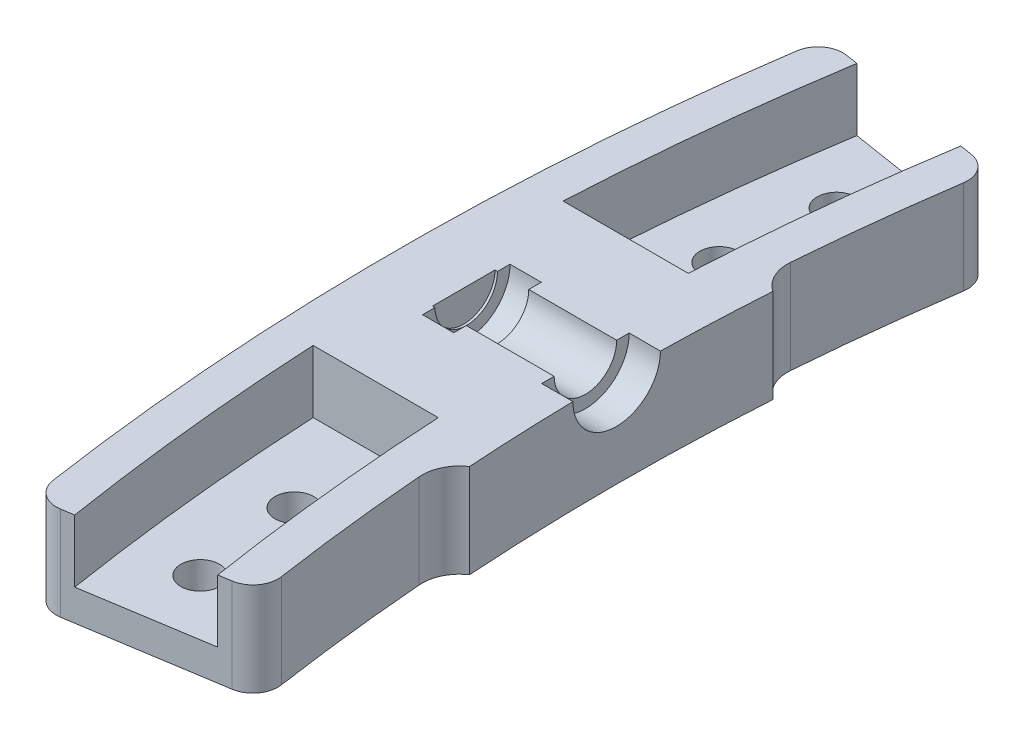
SolidWorks part; units mm, degrees
ref_plane "Front Plane" through (0, 0, 0) normal (0, 0, 1) x (1, 0, 0)
ref_plane "Top Plane" through (0, 0, 0) normal (0, 1, 0) x (1, 0, 0)
ref_plane "Right Plane" through (0, 0, 0) normal (1, 0, 0) x (0, 0, -1)
sketch "Sketch1" plane through (0, 0, 0) normal (0, 1, 0) x (1, 0, 0)
  line L0 (0, 0) -> (-197.5377, -31.2869) construction
  line L1 (0, 0) -> (-197.5377, 31.2869) construction
  line L2 (0, 0) -> (-195, 0) construction
  line L3 (-197.5377, 31.2869) -> (-187.6608, 29.7225)
  line L4 (-187.6608, -29.7225) -> (-197.5377, -31.2869)
  line L5 (0, 0) -> (-200.5007, -31.7562) construction
  line L6 (0, 0) -> (-200.5007, 31.7562) construction
  line L7 (-200.5007, 31.7562) -> (-184.6977, 29.2532)
  line L8 (-200.5007, -31.7562) -> (-184.6977, -29.2532)
  arc A0 (-197.5377, 31.2869) -> (-197.5377, -31.2869) centre (0, 0) ccw
  arc A1 (-187.6608, 29.7225) -> (-187.6608, -29.7225) centre (0, 0) ccw
  arc A2 (-192.5992, -30.5047) -> (-192.5992, 30.5047) centre (0, 0) cw construction
  arc A4 (-184.6977, 29.2532) -> (-184.6977, -29.2532) centre (0, 0) ccw
  arc A5 (-200.5007, 31.7562) -> (-200.5007, -31.7562) centre (0, 0) ccw
  dimension "D1" = 200
  dimension "D2" = 190
  dimension "D3" = 5
  dimension "D5" = 187
  dimension "D6" = 203
  dimension "D4" = 18
extrude "Boss-Extrude1" add sketch "Sketch1" along normal blind 10 contours A1 L3 A0 L4 | L7 A5 L8 A0 | A4 L7 A1 L8 region at (-200.6761, 0, 0) region at (-194.2416, 0, 0) region at (-187.7297, 0, 0)
ref_plane "Plane1" through (-195, 0, 0) normal (1, 0, 0) x (0, 0, -1)
sketch "Sketch15" plane through (0, 10, 0) normal (0, 1, 0) x (1, 0, 0)
  line L0 (-187.6608, -29.7225) -> (-197.5377, -31.2869) construction
  line L1 (-185, 10) -> (-205, 10)
  line L2 (-185, 10) -> (-185, -10)
  line L3 (-185, -10) -> (-205, -10)
  line L4 (-205, 10) -> (-205, -10)
  line L5 (-185, 10) -> (-205, -10) construction
  line L6 (-185, -10) -> (-205, 10) construction
  line L7 (-197.5377, 31.2869) -> (-187.6608, 29.7225) construction
  line L8 (-187.6608, -29.7225) -> (-197.5377, -31.2869)
  line L9 (-197.5377, 31.2869) -> (-187.6608, 29.7225)
  arc A2 (-187.6608, 29.7225) -> (-187.6608, -29.7225) centre (0, 0) ccw construction
  arc A3 (-197.5377, 31.2869) -> (-197.5377, -31.2869) centre (0, 0) ccw construction
  arc A4 (-187.6608, 29.7225) -> (-187.6608, -29.7225) centre (0, 0) ccw
  arc A5 (-197.5377, 31.2869) -> (-197.5377, -31.2869) centre (0, 0) ccw
  point P0 (-195, 0)
  line M5 (-200.5007, -31.7562) -> (-184.6977, -29.2532)
  line M7 (-184.6977, 29.2532) -> (-200.5007, 31.7562)
  dimension "D1" = 20
  dimension "D2" = 20
extrude "Cut-Extrude1" cut sketch "Sketch15" against normal blind 5 contours A5 L1 A4 M7 | L3 A5 A4 M5 region at (-193.9153, 10, -20.2762) region at (-193.9153, 10, 20.2762)
ref_plane "Plane2" through (-195, 0, 0) normal (-1, 0, 0) x (0, 0, 1)
sketch "Sketch12" plane through (0, 0, 0) normal (0, 1, 0) x (1, 0, 0)
  line L0 (0, 0) -> (-194.258, -16.9954) construction
  line L1 (0, 0) -> (-193.3317, -25.4526) construction
  line L2 (0, 0) -> (-195, 0) construction
  line L3 (0, 0) -> (-195, 0) construction
  line L4 (0, 0) -> (-194.258, 16.9954) construction
  line L5 (0, 0) -> (-193.3317, 25.4526) construction
  arc A0 (-192.5992, 30.5047) -> (-192.5992, -30.5047) centre (0, 0) ccw construction
  dimension "D1" = 10
  dimension "D2" = 15
hole_wizard "Ø3.1 (3.1) Diameter Hole2" positions "Sketch18" profile "Sketch17" hole size "Ø3.1" standard "ISO" end condition through all
sketch "Sketch18" plane through (0, 0, 0) normal (0, -1, 0) x (-1, 0, 0)
  point P0 (193.3317, -25.4526)
  point P3 (194.258, -16.9954)
  point P6 (194.258, 16.9954)
  point P9 (193.3317, 25.4526)
sketch "Sketch17" plane through (-193.3317, 0, 25.4526) normal (1, 0, 0) x (0, 0, -1)
  line L0 (0, 0) -> (0, 10)
  line L1 (0, 10) -> (1.55, 10)
  line L2 (1.55, 10) -> (1.55, 0)
  line L5 (1.55, 0) -> (0, 0)
  line L11 (0, -6.35) -> (0, 107.95) construction
  dimension "Thru Hole Dia." = 3.1
  dimension "Thru Hole Depth" = 10
sketch "Sketch19" plane through (0, 0, 0) normal (0, 1, 0) x (1, 0, 0)
  line L0 (0, 0) -> (-185.1028, -12.1323) construction
  line L1 (0, 0) -> (-185.5, 0) construction
  line L2 (-185.1028, -12.1323) -> (-186.5996, -12.2304)
  line L3 (-185.1028, 12.1323) -> (-186.5996, 12.2304)
  arc A0 (-185.1028, 12.1323) -> (-185.1028, -12.1323) centre (0, 0) ccw
  arc A1 (-184.6977, 29.2532) -> (-184.6977, -29.2532) centre (0, 0) ccw construction
  arc A2 (-186.5996, 12.2304) -> (-186.5996, -12.2304) centre (0, 0) ccw
  dimension "D1" = 185.5
  dimension "D2" = 3.75
extrude "Boss-Extrude2" add sketch "Sketch19" along normal blind 10
fillet "Fillet1" radius 3 2 edges at (-186.5996, 5, -12.2304) (-186.5996, 5, 12.2304)
fillet "Fillet2" radius 2 4 edges at (-200.5007, 5, -31.7562) (-200.5007, 5, 31.7562) (-184.6977, 5, 29.2532) (-184.6977, 5, -29.2532)
sketch "Sketch20" plane through (0, 10, 0) normal (0, 1, 0) x (1, 0, 0)
  line L0 (0, 0) -> (-185, 0) construction
  line L1 (-185, 0) -> (-197.5, 0) construction
  dimension "D1" = 185
  dimension "D2" = 12.5
ref_plane "Plane3" through (-197.5, 0, 0) normal (1, 0, 0) x (0, 0, -1)
sketch "Sketch21" plane through (-197.5, 0, 0) normal (1, 0, 0) x (0, 0, -1)
  line L0 (12.1323, 10) -> (-12.1323, 10) construction
  circle A0 centre (0, 10) radius 2.1
  dimension "D1" = 4.2
extrude "Cut-Extrude2" cut sketch "Sketch21" along normal through all
sketch "Sketch22" plane through (-197.5, 0, 0) normal (1, 0, 0) x (0, 0, -1)
  line L0 (-2.1, 10) -> (2.1, 10) construction
  circle A0 centre (0, 10) radius 3.5
  dimension "D1" = 7
extrude "Cut-Extrude3" cut sketch "Sketch22" along normal blind 2.5
sketch "Sketch23" plane through (-197.5, 0, 0) normal (1, 0, 0) x (0, 0, -1)
  line L0 (-3.5, 10) -> (3.5, 10) construction
  circle A0 centre (0, 10) radius 2.5
  dimension "D1" = 5
extrude "Cut-Extrude4" cut sketch "Sketch23" against normal blind 0.2 and the other way blind 2.7
sketch "Sketch24" plane through (0, 10, 0) normal (0, 1, 0) x (1, 0, 0)
  line L0 (-185.5, 0) -> (-197.7, 0) construction
  line L1 (-197.7, -2.5) -> (-197.7, 2.5) construction
  line L3 (-187.967, 0) -> (-185.467, 0)
  line L4 (-187.967, 0) -> (-187.967, 3.5)
  line L5 (-187.967, 3.5) -> (-185.467, 3.5)
  line L6 (-185.467, 0) -> (-185.467, 3.5)
  arc A0 (-185.4881, 2.1) -> (-185.4881, -2.1) centre (0, 0) ccw construction
  arc A1 (-185.1028, 12.1323) -> (-185.4881, 2.1) centre (0, 0) ccw construction
  dimension "D1" = 2.5
  dimension "D2" = 7
revolve "Cut-Revolve1" cut sketch "Sketch24" angle 360 about L0
sketch "Sketch25" plane through (-187.967, 0, 0) normal (1, 0, 0) x (0, 0, -1)
  line L0 (-2.5, 10) -> (2.5, 10) construction
  circle A0 centre (0, 10) radius 2.5
  dimension "D1" = 5
extrude "Cut-Extrude5" cut sketch "Sketch25" against normal up to surface (9.733 mm away) up to face at (-197.7, 8.75, 0)
sketch "Sketch26" plane through (0, 0, 0) normal (0, -1, 0) x (1, 0, 0)
  line L2 (-198.5155, -31.4418) -> (-186.6626, -29.5645)
  line L3 (-186.6626, 29.5645) -> (-198.5155, 31.4418)
  line L4 (-198.5155, -31.4418) -> (-186.6626, -29.5645)
  line L5 (-186.6626, 29.5645) -> (-198.5155, 31.4418)
  arc A10 (-200.8068, 29.7596) -> (-200.8068, -29.7596) centre (0, 0) ccw
  arc A11 (-200.8068, -29.7596) -> (-198.5155, -31.4418) centre (-198.8284, -29.4664) ccw
  arc A12 (-186.6626, -29.5645) -> (-184.9969, -27.2971) centre (-186.9755, -27.5891) ccw
  arc A13 (-186.4092, -14.8532) -> (-184.9969, -27.2971) centre (0, 0) ccw
  arc A14 (-185.1028, -12.1323) -> (-186.4092, -14.8532) centre (-183.4187, -14.6149) ccw
  arc A15 (-185.1028, 12.1323) -> (-185.1028, -12.1323) centre (0, 0) ccw
  arc A16 (-186.4092, 14.8532) -> (-185.1028, 12.1323) centre (-183.4187, 14.6149) ccw
  arc A17 (-184.9969, 27.2971) -> (-186.4092, 14.8532) centre (0, 0) ccw
  arc A18 (-184.9969, 27.2971) -> (-186.6626, 29.5645) centre (-186.9755, 27.5891) ccw
  arc A19 (-198.5155, 31.4418) -> (-200.8068, 29.7596) centre (-198.8284, 29.4664) ccw
  arc A20 (-200.8068, 29.7596) -> (-200.8068, -29.7596) centre (0, 0) ccw
  arc A21 (-200.8068, -29.7596) -> (-198.5155, -31.4418) centre (-198.8284, -29.4664) ccw
  arc A22 (-186.6626, -29.5645) -> (-184.9969, -27.2971) centre (-186.9755, -27.5891) ccw
  arc A23 (-186.4092, -14.8532) -> (-184.9969, -27.2971) centre (0, 0) ccw
  arc A24 (-185.1028, -12.1323) -> (-186.4092, -14.8532) centre (-183.4187, -14.6149) ccw
  arc A25 (-185.1028, 12.1323) -> (-185.1028, -12.1323) centre (0, 0) ccw
  arc A26 (-186.4092, 14.8532) -> (-185.1028, 12.1323) centre (-183.4187, 14.6149) ccw
  arc A27 (-184.9969, 27.2971) -> (-186.4092, 14.8532) centre (0, 0) ccw
  arc A28 (-184.9969, 27.2971) -> (-186.6626, 29.5645) centre (-186.9755, 27.5891) ccw
  arc A29 (-198.5155, 31.4418) -> (-200.8068, 29.7596) centre (-198.8284, 29.4664) ccw
  dimension "D1" = 0
extrude "Cut-Extrude6" cut sketch "Sketch26" against normal blind 2.5
